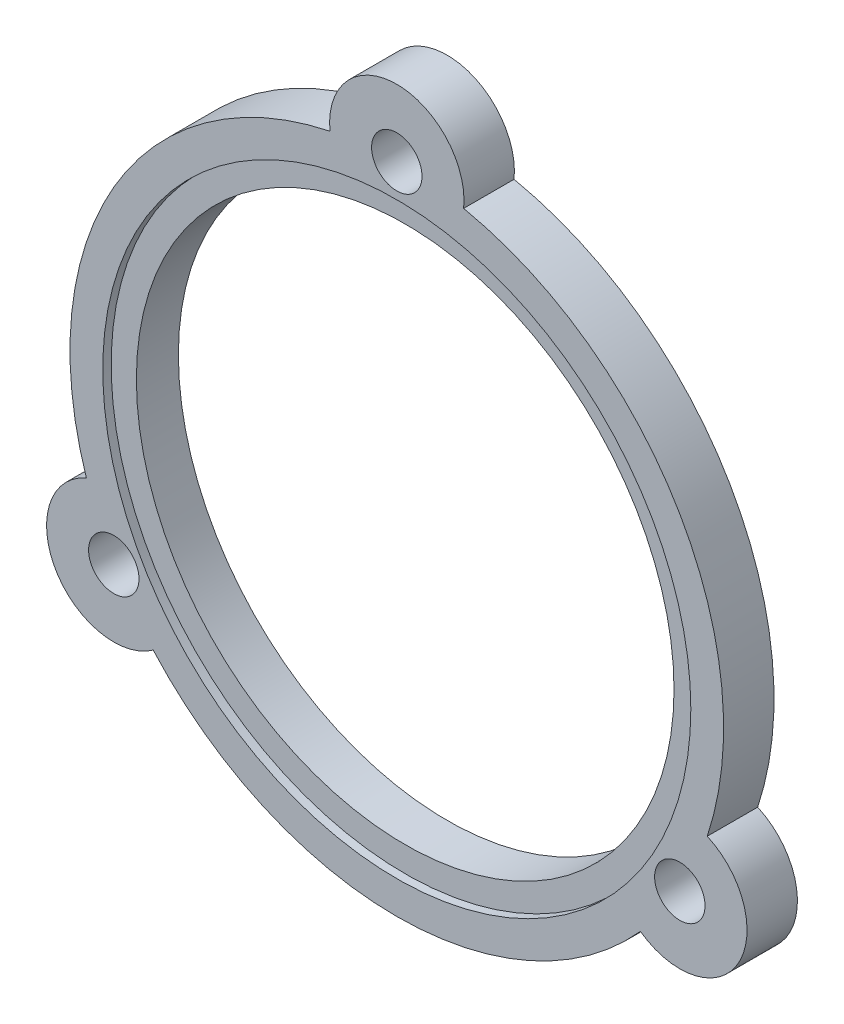
SolidWorks part; units mm, degrees
material "PLA"
ref_plane "Front" through (0, 0, 0) normal (0, 0, 1) x (1, 0, 0)
ref_plane "Top" through (0, 0, 0) normal (0, 1, 0) x (1, 0, 0)
ref_plane "Right" through (0, 0, 0) normal (1, 0, 0) x (0, 0, -1)
other "Configuration Table"
sketch "Esquisse1" plane through (0, 0, 0) normal (0, 0, 1) x (1, 0, 0)
  line L0 (0, 0) -> (0, 19.45) construction
  circle A0 centre (0, 19.45) radius 1.5
  circle A2 centre (0, 19.45) radius 4
  circle A3 centre (0, 0) radius 19.45
  circle A4 centre (0, 0) radius 16
  dimension "D1" = 3
  dimension "D2" = 8
  dimension "D3" = 38.9
  dimension "D4" = 32
extrude "Boss.-Extru.1" add sketch "Esquisse1" along normal blind 3 contours A4 A2 A3 | L0 A2 A3 A0 | L0 A0 A3 | A0 L0 A3 | A2 L0 A0 A3 region at (-1.888, 17.6131, 0) region at (1.888, 17.6131, 0) region at (-11.0101, -12.3527, 0) region at (-0.6285, 18.8031, 0) region at (0.6285, 18.8031, 0)
extrude "Enlèv. mat.-Extru.1" cut sketch "Esquisse1<12>" along normal up to surface (3 mm away) contours L0 A0 A3 | A0 L0 A3 region at (-0.6285, 18.8031, 0) region at (0.6285, 18.8031, 0) up to face at (19.45, 0, 3)
sketch "Esquisse1<12>" plane through (0, 0, 0) normal (0, 0, 1) x (1, 0, 0) same geometry as "Esquisse1"
extrude "Boss.-Extru.2" add sketch "Esquisse1<13>" along normal up to surface (3 mm away) contours A3 A2 A0 region at (0, 21.2294, 0) up to face at (0, -0.75, 3)
sketch "Esquisse1<13>" plane through (0, 0, 0) normal (0, 0, 1) x (1, 0, 0) same geometry as "Esquisse1"
pattern_circular "Répétition circulaire1" count 2 every 120 about axis through (0, 0, 3) along (0, 0, -1) of "Enlèv. mat.-Extru.1", "Boss.-Extru.2" other way count 2
sketch "Esquisse2" plane through (0, 0, 3) normal (0, 0, 1) x (1, 0, 0)
  circle A0 centre (0, 0) radius 17.5
  dimension "D1" = 35
extrude "Enlèv. mat.-Extru.2" cut sketch "Esquisse2" against normal blind 0.5
